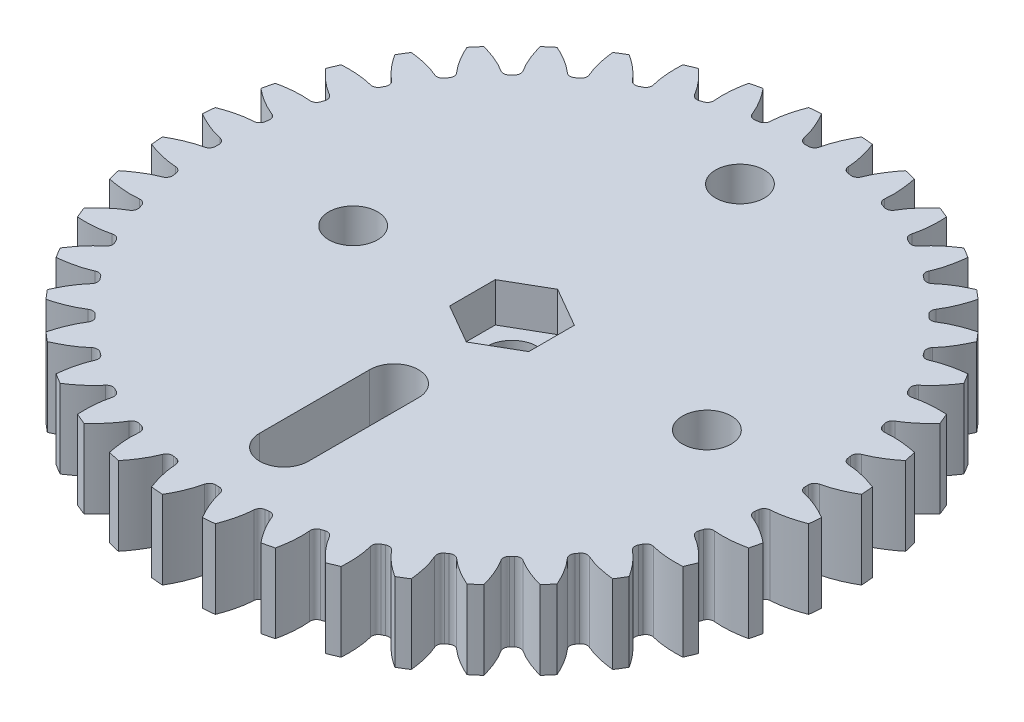
SolidWorks part; units mm, degrees
ref_plane "Front Plane" through (0, 0, 0) normal (0, 0, 1) x (1, 0, 0)
ref_plane "Top Plane" through (0, 0, 0) normal (0, 1, 0) x (1, 0, 0)
ref_plane "Right Plane" through (0, 0, 0) normal (1, 0, 0) x (0, 0, -1)
sketch "Sketch2" plane through (0, 0, 0) normal (0, 1, 0) x (1, 0, 0)
  circle A0 centre (0, 0) radius 53.34
  dimension "D1" = 106.68
extrude "Boss-Extrude1" add sketch "Sketch2" along normal blind 12.7
sketch "Sketch3" plane through (0, 0, 0) normal (0, -1, 0) x (-1, 0, 0)
  line L0 (0, 0) -> (47.7222, -1.163) construction
  line L1 (0, 0) -> (47.7222, 1.163) construction
  line L2 (47.7222, -1.163) -> (47.6109, -1.1603)
  line L3 (47.7222, 1.163) -> (47.6109, 1.1603)
  circle A0 centre (0, 0) radius 53.34
  circle A1 centre (0, 0) radius 50.8
  circle A2 centre (0, 0) radius 47.752
  circle A3 centre (0, 0) radius 47.625
  spline S0 degree 4 poles (47.7222, 1.163) (47.731, 1.1633) (47.7556, 1.1645) (47.802, 1.1678) (47.8777, 1.1747) (47.9741, 1.186) (48.0986, 1.2033) (48.2451, 1.2271) (48.4058, 1.257) (48.5805, 1.2934) (48.7546, 1.3332) (48.928, 1.3762) (49.1005, 1.4219) (49.3093, 1.4808) (49.5592, 1.5562) (49.8507, 1.6513) (50.1805, 1.7675) (50.5158, 1.8948) (50.845, 2.0273) (51.1768, 2.1695) (51.4972, 2.313) (51.8289, 2.4707) (52.1347, 2.6205) (52.4761, 2.7979) (52.7513, 2.9438) (53.113, 3.1463) (53.3263, 3.2689) (53.5754, 3.4159) (53.6857, 3.483) (53.7537, 3.5243) knots 0 0 0 0 0 0.005377 0.015084 0.028532 0.04661 0.064855 0.092111 0.119476 0.146842 0.174209 0.201575 0.228941 0.256307 0.307035 0.361767 0.4165 0.471232 0.525964 0.580697 0.635429 0.690161 0.744894 0.799626 0.854358 0.909091 0.954545 1 1 1 1 1 construction
  spline S1 degree 4 poles (47.7222, 1.163) (47.731, 1.1633) (47.7556, 1.1645) (47.802, 1.1678) (47.8777, 1.1747) (47.9741, 1.186) (48.0986, 1.2033) (48.2451, 1.2271) (48.4058, 1.257) (48.5805, 1.2934) (48.7546, 1.3332) (48.928, 1.3762) (49.1005, 1.4219) (49.3093, 1.4808) (49.5592, 1.5562) (49.8507, 1.6513) (50.1805, 1.7675) (50.5158, 1.8948) (50.845, 2.0273) (51.1768, 2.1695) (51.4972, 2.313) (51.8289, 2.4707) (52.1347, 2.6205) (52.4761, 2.7979) (52.7513, 2.9438) (53.0346, 3.1024) (53.1723, 3.1808) (53.2426, 3.2213) knots 0 0 0 0 0 0.005377 0.015084 0.028532 0.04661 0.064855 0.092111 0.119476 0.146842 0.174209 0.201575 0.228941 0.256307 0.307035 0.361767 0.4165 0.471232 0.525964 0.580697 0.635429 0.690161 0.744894 0.799626 0.854358 0.909091 0.909091 0.909091 0.909091 0.909091
  spline S2 degree 4 poles (47.7222, -1.163) (47.731, -1.1633) (47.7556, -1.1645) (47.802, -1.1678) (47.8777, -1.1747) (47.9741, -1.186) (48.0986, -1.2033) (48.2451, -1.2271) (48.4058, -1.257) (48.5805, -1.2934) (48.7546, -1.3332) (48.928, -1.3762) (49.1005, -1.4219) (49.3093, -1.4808) (49.5592, -1.5562) (49.8507, -1.6513) (50.1805, -1.7675) (50.5158, -1.8948) (50.845, -2.0273) (51.1768, -2.1695) (51.4972, -2.313) (51.8289, -2.4707) (52.1347, -2.6205) (52.4761, -2.7979) (52.7513, -2.9438) (53.113, -3.1463) (53.3263, -3.2689) (53.5754, -3.4159) (53.6857, -3.483) (53.7537, -3.5243) knots 0 0 0 0 0 0.005377 0.015084 0.028532 0.04661 0.064855 0.092111 0.119476 0.146842 0.174209 0.201575 0.228941 0.256307 0.307035 0.361767 0.4165 0.471232 0.525964 0.580697 0.635429 0.690161 0.744894 0.799626 0.854358 0.909091 0.954545 1 1 1 1 1 construction
  spline S3 degree 4 poles (47.7222, -1.163) (47.731, -1.1633) (47.7556, -1.1645) (47.802, -1.1678) (47.8777, -1.1747) (47.9741, -1.186) (48.0986, -1.2033) (48.2451, -1.2271) (48.4058, -1.257) (48.5805, -1.2934) (48.7546, -1.3332) (48.928, -1.3762) (49.1005, -1.4219) (49.3093, -1.4808) (49.5592, -1.5562) (49.8507, -1.6513) (50.1805, -1.7675) (50.5158, -1.8948) (50.845, -2.0273) (51.1768, -2.1695) (51.4972, -2.313) (51.8289, -2.4707) (52.1347, -2.6205) (52.4761, -2.7979) (52.7513, -2.9438) (53.0346, -3.1024) (53.1723, -3.1808) (53.2426, -3.2213) knots 0 0 0 0 0 0.005377 0.015084 0.028532 0.04661 0.064855 0.092111 0.119476 0.146842 0.174209 0.201575 0.228941 0.256307 0.307035 0.361767 0.4165 0.471232 0.525964 0.580697 0.635429 0.690161 0.744894 0.799626 0.854358 0.909091 0.909091 0.909091 0.909091 0.909091
  dimension "D1" = 106.68
  dimension "D2" = 101.6
  dimension "D3" = 95.504
  dimension "D4" = 95.25
extrude "Cut-Extrude1" cut sketch "Sketch3" against normal blind 12.7 contours A1 S3 A0 S1 | A2 S3 A1 S1 | L2 S3 A2 S1 L3 A3 region at (-47.6838, 0, 0) region at (-49.4115, 0, 0) region at (-52.1487, 0, 0)
fillet "Fillet2" radius 1.016 2 edges at (-47.6109, 6.35, -1.1603) (-47.6109, 6.35, 1.1603)
pattern_circular "CirPattern1" count 40 over 360 about axis through (0, 12.7, 0) along (0, 1, 0) of "Fillet2", "Cut-Extrude1"
sketch "Sketch4" plane through (0, 12.7, 0) normal (0, 1, 0) x (1, 0, 0)
  circle A0 centre (0, 0) radius 4.0957
  dimension "D1" = 8.1915
extrude "Cut-Extrude2" cut sketch "Sketch4" against normal through all
sketch "Sketch5" plane through (0, 12.7, 0) normal (0, 1, 0) x (1, 0, 0)
  line L1 (0, 7.3763) -> (-6.3881, 3.6882)
  line L2 (-6.3881, 3.6882) -> (-6.3881, -3.6882)
  line L3 (-6.3881, -3.6882) -> (0, -7.3763)
  line L4 (0, -7.3763) -> (6.3881, -3.6882)
  line L5 (6.3881, -3.6882) -> (6.3881, 3.6882)
  line L6 (6.3881, 3.6882) -> (0, 7.3763)
  circle A0 centre (0, 0) radius 6.3881 construction
  dimension "D1" = 12.7762
extrude "Cut-Extrude3" cut sketch "Sketch5" against normal blind 6.35
sketch "Sketch6" plane through (0, 12.7, 0) normal (0, 1, 0) x (1, 0, 0)
  line L0 (0, 0) -> (0, 36.83) construction
  line L1 (47.6243, -0.2629) -> (-47.6243, -0.2629) construction
  line L2 (0, 0) -> (0, -47.625) construction
  line L3 (0, -19.05) -> (0, -36.83) construction
  line L4 (3.937, -19.05) -> (3.937, -36.83)
  line L5 (-3.937, -19.05) -> (-3.937, -36.83)
  circle A0 centre (0, 36.83) radius 3.937
  arc A1 (-0.2629, -47.6243) -> (0.2629, -47.6243) centre (0, 0) ccw construction
  circle A2 centre (31.75, -0.2629) radius 3.937
  circle A3 centre (-25.4, -0.2629) radius 3.937
  arc A4 (3.937, -19.05) -> (-3.937, -19.05) centre (0, -19.05) ccw
  arc A5 (-3.937, -36.83) -> (3.937, -36.83) centre (0, -36.83) ccw
  point P18 (0, -27.94)
  dimension "D2" = 7.874
  dimension "D3" = 7.874
  dimension "D4" = 7.874
  dimension "D7" = 3.937
  dimension "D1" = 36.83
  dimension "D5" = 31.75
  dimension "D6" = 25.4
  dimension "D8" = 36.83
  dimension "D9" = 19.05
extrude "Cut-Extrude4" cut sketch "Sketch6" against normal through all both and the other way through all
equation "\"DiametralPitch\"= 10"
equation "\"NumTeeth\"= 40"
equation "\"PressureAngle\"= 20deg"
equation "\"Addendum\"= 1 / \"DiametralPitch\""
equation "\"Dedendum\"= 1.25 / \"DiametralPitch\""
equation "\"WorkingDepth\"= 2 / \"DiametralPitch\""
equation "\"WholeDepth\"= 2.25 / \"DiametralPitch\""
equation "\"Clearance\"= 0.3 / \"DiametralPitch\""
equation "\"ToothThickness\"= 1.5708 / \"DiametralPitch\""
equation "\"CircularPitch\"= pi / \"DiametralPitch\""
equation "\"PitchCircle\"= \"NumTeeth\" / \"DiametralPitch\""
equation "\"OutsideDiameter\"= ( \"NumTeeth\" + 2 ) / \"DiametralPitch\""
equation "\"Fillet\"= \"Clearance\" * cos ( \"PressureAngle\" ) * tan ( ( 90 + \"PressureAngle\" ) / 2 )"
equation "\"AddendumCircle\"= \"PitchCircle\" + ( 2 * \"Addendum\" )"
equation "\"DedendumCircle\"= \"PitchCircle\" - ( 2 * \"Dedendum\" )"
equation "\"BaseCircle\"= \"PitchCircle\" * cos ( \"PressureAngle\" )"
equation "\"PitchAngle\"= 360deg / \"NumTeeth\""
equation "\"Alpha\"= sqr ( \"PitchCircle\" ^ 2 - \"BaseCircle\" ^ 2 ) / \"BaseCircle\" * 180 / PI - \"PressureAngle\""
equation "\"Beta\"= ( \"PitchAngle\" / 4 - \"Alpha\" )"
equation "\"Phi\"= sqr ( ( \"AddendumCircle\" / 2 ) ^ 2 - ( \"BaseCircle\" / 2 ) ^ 2 ) / ( \"BaseCircle\" / 2 )"
